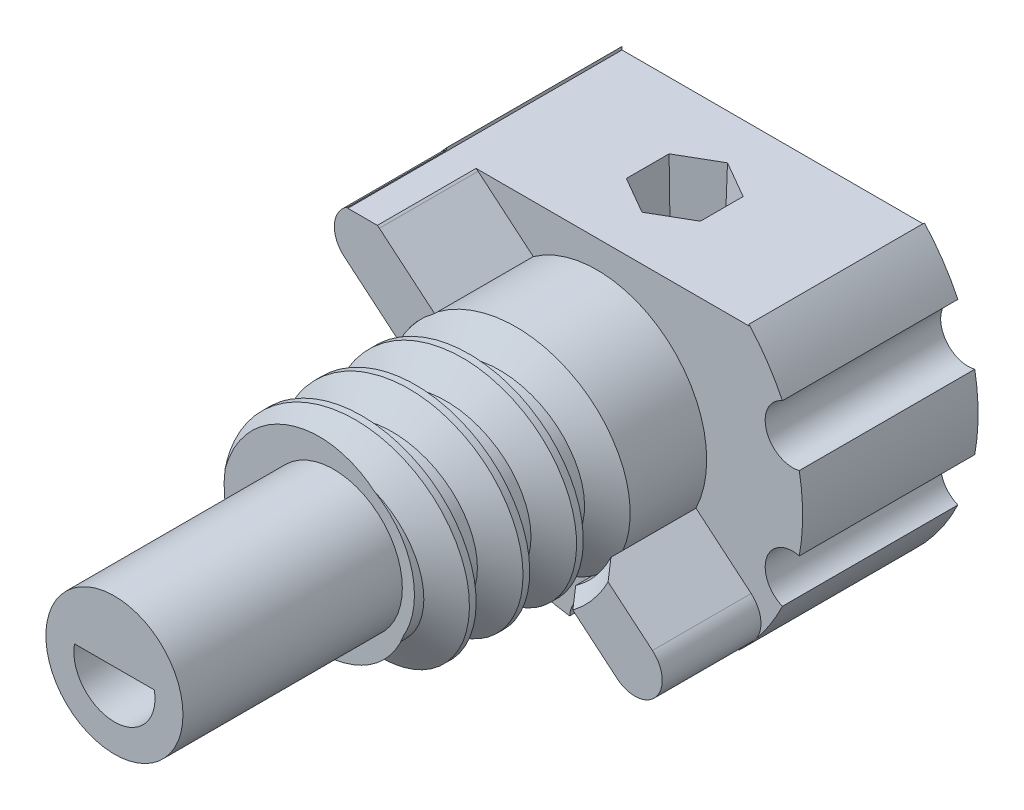
SolidWorks part; units mm, degrees
material "Custom Plastic"
ref_plane "Front" through (0, 0, 0) normal (0, 0, 1) x (1, 0, 0)
ref_plane "Top" through (0, 0, 0) normal (0, 1, 0) x (1, 0, 0)
ref_plane "Right" through (0, 0, 0) normal (1, 0, 0) x (0, 0, -1)
sketch "Sketch1" plane through (0, 0, 0) normal (0, 0, 1) x (1, 0, 0)
  line L0 (-1.7361, 0.82) -> (1.7361, 0.82) construction
  line L1 (0, 0.82) -> (0, -1.92) construction
  arc A0 (-1.7361, 0.82) -> (1.7361, 0.82) centre (0, 0) ccw construction
  circle A1 centre (0, 0) radius 7.5
  point P8 (0, 0)
  dimension "D1" = 2.74
  dimension "D2" = 1.92
extrude "Boss-Extrude1" add sketch "Sketch1" along normal blind 7
sketch "Sketch2" plane through (0, 0, 7) normal (0, 0, 1) x (1, 0, 0)
  circle A0 centre (0, 0) radius 4
extrude "Boss-Extrude2" add sketch "Sketch2" along normal blind 9
sketch "Sketch3" plane through (0, 0, 7) normal (0, 0, 1) x (1, 0, 0)
  line L0 (-7.5, 0) -> (7.5, 0) construction
  line L5 (5.7453, -4.8209) -> (-5.7453, 4.8209) construction
  line L6 (5.6221, -3.4121) -> (-4.3365, 4.9442)
  line L8 (4.3365, -4.9442) -> (-5.6221, 3.4121)
  circle A3 centre (0, 0) radius 7.5 construction
  arc A4 (4.3365, -4.9442) -> (5.6221, -3.4121) centre (4.9793, -4.1781) ccw
  arc A5 (-4.3365, 4.9442) -> (-5.6221, 3.4121) centre (-4.9793, 4.1781) ccw
  dimension "D6" = 2
  dimension "D7" = 2
  dimension "D5" = 40
extrude "Boss-Extrude3" add sketch "Sketch3" along normal blind 3
thread "Thread1" pitch 1.9538 method cut trim with start face yes profile "Thread Profile1" start angle 0, offset 1.75, length 8, pitch 1.9538, diameter 8
ref_plane "Plane1" through (-4, 0, 17.75) normal (0, -1, 0) x (-1, 0, 0)
sketch "Thread Profile1" plane through (-4, 0, 17.75) normal (0, -1, 0) x (-1, 0, 0)
  line L0 (0, 0) -> (0, 1.9538) construction
  line L11 (0, 0) -> (0, 1.7096)
  line L12 (0, 1.7096) -> (-1.0576, 1.099)
  line L13 (-1.0576, 1.099) -> (-1.0576, 0.6106)
  line L15 (-1.0576, 0.6106) -> (0, 0)
  line L17 (-1.0576, 0.8548) -> (0, 0.8548) construction
  point P2 (0, 0)
  dimension "Pitch" = 1.9538
  dimension "Profile_Angle" = 60
  dimension "Profile_Land" = 0.4885
  dimension "Profile_Height" = 1.0576
sketch "Sketch5" plane through (0, 0, 7) normal (0, 0, 1) x (1, 0, 0)
  line L3 (-4.3365, 4.9442) -> (-2.3241, 3.2556)
  line L4 (3.6097, -1.7235) -> (5.6221, -3.4121)
  line L5 (-4.3365, 4.9442) -> (-2.3241, 3.2556)
  line L6 (3.6097, -1.7235) -> (5.6221, -3.4121)
  line L7 (-3.6097, 1.7235) -> (-5.6221, 3.4121)
  line L8 (4.3365, -4.9442) -> (2.3241, -3.2556)
  line L9 (-3.6097, 1.7235) -> (-5.6221, 3.4121)
  line L10 (4.3365, -4.9442) -> (2.3241, -3.2556)
  arc A0 (-3.6097, 1.7235) -> (2.3241, -3.2556) centre (0, 0) ccw
  arc A1 (3.6097, -1.7235) -> (-2.3241, 3.2556) centre (0, 0) ccw
  arc A4 (5.7453, -4.8209) -> (-5.7453, 4.8209) centre (0, 0) ccw
  arc A5 (-4.3365, 4.9442) -> (-5.7453, 4.8209) centre (-4.9793, 4.1781) ccw
  arc A6 (3.6097, -1.7235) -> (-2.3241, 3.2556) centre (0, 0) ccw
  arc A7 (5.7453, -4.8209) -> (5.6221, -3.4121) centre (4.9793, -4.1781) ccw
  arc A8 (5.7453, -4.8209) -> (-5.7453, 4.8209) centre (0, 0) ccw
  arc A9 (-4.3365, 4.9442) -> (-5.7453, 4.8209) centre (-4.9793, 4.1781) ccw
  arc A11 (5.7453, -4.8209) -> (5.6221, -3.4121) centre (4.9793, -4.1781) ccw
  arc A12 (-3.6097, 1.7235) -> (2.3241, -3.2556) centre (0, 0) ccw
  arc A13 (-5.7453, 4.8209) -> (-5.6221, 3.4121) centre (-4.9793, 4.1781) ccw
  arc A14 (-5.7453, 4.8209) -> (5.7453, -4.8209) centre (0, 0) ccw
  arc A15 (4.3365, -4.9442) -> (5.7453, -4.8209) centre (4.9793, -4.1781) ccw
  arc A17 (-5.7453, 4.8209) -> (-5.6221, 3.4121) centre (-4.9793, 4.1781) ccw
  arc A18 (-5.7453, 4.8209) -> (5.7453, -4.8209) centre (0, 0) ccw
  arc A19 (4.3365, -4.9442) -> (5.7453, -4.8209) centre (4.9793, -4.1781) ccw
  arc M13 (5.7453, -4.8209) -> (-5.7453, 4.8209) centre (0, 0) ccw
  arc M14 (-5.7453, 4.8209) -> (-4.3365, 4.9442) centre (-4.9793, 4.1781) cw
  line M15 (-4.3365, 4.9442) -> (-2.3241, 3.2556)
  line M17 (3.6097, -1.7235) -> (5.6221, -3.4121)
  arc M18 (5.6221, -3.4121) -> (5.7453, -4.8209) centre (4.9793, -4.1781) cw
  dimension "D1" = 0
  dimension "D2" = 0
extrude "Cut-Extrude1" cut sketch "Sketch5" against normal blind 0.6 contours A1 M17 M18 M13 M14 M15 | A19 L10 A0 L9 A17 A18 region at (2.6743, 3.1871, 7) region at (-2.6743, -3.1871, 7)
sketch "Sketch6" plane through (0, 0, 0) normal (0, 0, -1) x (-1, 0, 0)
  circle A0 centre (0, 7.5) radius 1
  circle A1 centre (0, 0) radius 7.5 construction
  dimension "D1" = 2
extrude "Cut-Extrude2" cut sketch "Sketch6" against normal up to surface (6.4 mm away) up to face at (1.5978, 1.9042, 6.4)
pattern_circular "CirPattern1" count 10 over 360 about axis through (0, 0, 7) along (0, 0, -1) of "Cut-Extrude2"
ref_plane "Plane2" through (0, 5, 0) normal (0, 1, 0) x (1, 0, 0)
sketch "Sketch8" plane through (0, 5, 0) normal (0, 1, 0) x (1, 0, 0)
  line L1 (5.5416, -13.865) -> (-5.4868, -13.865)
  line L2 (5.5416, -13.865) -> (5.5416, 0)
  line L3 (5.5416, 0) -> (-5.4868, 0)
  line L4 (-5.4868, -13.865) -> (-5.4868, 0)
  line L5 (5.5416, -13.865) -> (-5.4868, 0) construction
  line L6 (5.5416, 0) -> (-5.4868, -13.865) construction
  point P4 (0.0274, -6.9325)
extrude "Cut-Extrude3" cut sketch "Sketch8" along normal through all
sketch "Sketch9" plane through (0, 5, 0) normal (0, 1, 0) x (1, 0, 0)
  line L0 (0, 0) -> (0, -6.4) construction
  line L2 (-2.2913, -6.4) -> (2.2913, -6.4) construction
  line L3 (0, -1.6412) -> (-1.35, -2.4206)
  line L4 (-1.35, -2.4206) -> (-1.35, -3.9794)
  line L5 (-1.35, -3.9794) -> (0, -4.7588)
  line L6 (0, -4.7588) -> (1.35, -3.9794)
  line L7 (1.35, -3.9794) -> (1.35, -2.4206)
  line L8 (1.35, -2.4206) -> (0, -1.6412)
  circle A1 centre (0, -3.2) radius 1.35 construction
  dimension "D1" = 2.7
extrude "Cut-Extrude4" cut sketch "Sketch9" against normal blind 6 draft 2
sketch "Sketch10" plane through (0, 0, 16) normal (0, 0, 1) x (1, 0, 0)
  circle A0 centre (0, 0) radius 2.5
  dimension "D1" = 5
extrude "Boss-Extrude6" add sketch "Sketch10" along normal blind 8
chamfer "Chamfer2" distance 0.5 angle 45 1 edges
ref_plane "Plane3" through (0, 0, 10) normal (0, 0, 1) x (1, 0, 0)
sketch "Sketch15" plane through (0, 0, 0) normal (0, 0, -1) x (-1, 0, 0)
  line L0 (-1.8283, 0.76) -> (1.8283, 0.76)
  line L1 (0, 0.76) -> (0, -1.98) construction
  arc A1 (-1.8283, 0.76) -> (1.8283, 0.76) centre (0, 0) ccw
  point P7 (0, 0)
  dimension "D1" = 2.74
  dimension "D2" = 1.98
extrude "Cut-Extrude5" cut sketch "Sketch15" against normal through all
sketch "Sketch14" plane through (0, 0, 24) normal (0, 0, 1) x (1, 0, 0)
  line L6 (1.457, 0.26) -> (-1.457, 0.26)
  line L7 (1.457, 0.26) -> (-1.457, 0.26)
  circle A7 centre (0, 0) radius 2.0304
  arc A8 (-1.457, 0.26) -> (1.457, 0.26) centre (0, 0) ccw
  arc A10 (-1.457, 0.26) -> (1.457, 0.26) centre (0, 0) ccw
  arc M24 (1.8283, 0.76) -> (-1.8283, 0.76) centre (0, 0) cw
  line M25 (-1.8283, 0.76) -> (1.8283, 0.76)
  dimension "D1" = 0.5
extrude "Boss-Extrude7" add sketch "Sketch14" against normal blind 13.5 contours A7 M25 M24 | A10 L7 M24 M25 region at (0, 1.0556, 24) region at (0, -1.9318, 24)
chamfer "Chamfer4" distance 1 angle 45 2 edges at (0, 0.76, 0) (0, -1.98, 0)
chamfer "Chamfer5" distance 0.42 angle 50 2 edges at (0, -1.48, 10.5) (0, 0.26, 10.5) first distance on face at (0, -0.61, 17.25) first distance on face at (0, 0.26, 17.25)
